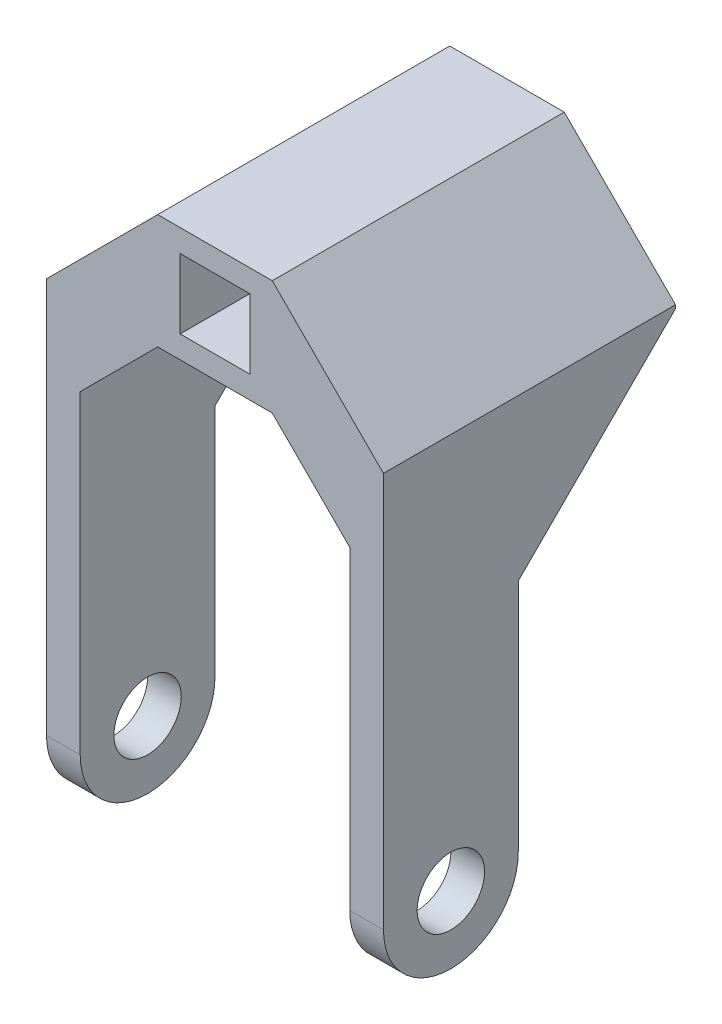
SolidWorks part; units mm, degrees
ref_plane "Front Plane" through (0, 0, 0) normal (0, 0, 1) x (1, 0, 0)
ref_plane "Top Plane" through (0, 0, 0) normal (0, 1, 0) x (1, 0, 0)
ref_plane "Right Plane" through (0, 0, 0) normal (1, 0, 0) x (0, 0, -1)
sketch "Sketch1" plane through (0, 0, 0) normal (0, 0, 1) x (1, 0, 0)
  line L1 (-50, 100) -> (50, 100) construction
  line L2 (-50, 100) -> (-50, -100) construction
  line L3 (-50, -100) -> (50, -100) construction
  line L4 (50, 100) -> (50, -100) construction
  line L5 (-50, 100) -> (50, -100)
  line L6 (-50, -100) -> (50, 100)
  point P0 (0, 0)
  dimension "D1" = 200
  dimension "D2" = 100
sketch "Sketch2" plane through (0, 0, 0) normal (0, 0, 1) x (1, 0, 0)
  line L0 (-25.5, 174.5) -> (25.5, 174.5)
  line L1 (-15.5, 215.5) -> (15.5, 215.5)
  line L2 (-15.5, 215.5) -> (-15.5, 184.5)
  line L3 (-15.5, 184.5) -> (15.5, 184.5)
  line L4 (15.5, 215.5) -> (15.5, 184.5)
  line L5 (-15.5, 215.5) -> (15.5, 184.5) construction
  line L6 (-15.5, 184.5) -> (15.5, 215.5) construction
  line L7 (25.5, 174.5) -> (60, 140)
  line L8 (60, 140) -> (60, -30)
  line L9 (60, -30) -> (75, -30)
  line L10 (75, -30) -> (75, 176)
  line L11 (75, 176) -> (25.5, 225.5)
  line L12 (25.5, 225.5) -> (-25.5, 225.5)
  line L13 (0, -110) -> (0, 110) construction
  line L14 (-60, -30) -> (-75, -30)
  line L15 (-60, 140) -> (-60, -30)
  line L16 (-75, -30) -> (-75, 176)
  line L17 (-25.5, 174.5) -> (-60, 140)
  line L18 (-75, 176) -> (-25.5, 225.5)
  point P0 (0, 200)
  point P10 (0, 0)
  point P15 (0, 0)
  point P23 (0, 174.5)
  point P24 (0, 225.5)
  dimension "D1" = 31
  dimension "D2" = 200
  dimension "D3" = 60
  dimension "D4" = 75
  dimension "D5" = 135
  dimension "D6" = 135
  dimension "D7" = 10
  dimension "D8" = 10
  dimension "D9" = 10
  dimension "D10" = 10
  dimension "D11" = 30
extrude "Boss-Extrude1" add sketch "Sketch2" along normal blind 30 and the other way blind 100
sketch "Sketch3" plane through (0, 0, 0) normal (1, 0, 0) x (0, 0, -1)
  line L0 (30, -30) -> (30, 104.5)
  line L1 (100, -30) -> (-30, -30) construction
  line L2 (30, 104.5) -> (100, 174.5)
  line L3 (100, 174.5) -> (100, -30)
  line L4 (100, -30) -> (100, 176) construction
  line L5 (100, -30) -> (30, -30)
  dimension "D1" = 30
  dimension "D2" = 45
extrude "Cut-Extrude1" cut sketch "Sketch3" against normal through all both and the other way through all
sketch "Sketch4" plane through (0, 0, 0) normal (1, 0, 0) x (0, 0, -1)
  circle A0 centre (0, 0) radius 15
  dimension "D1" = 30
extrude "Cut-Extrude2" cut sketch "Sketch4" against normal through all both and the other way through all
fillet "Fillet1" radius 30 4 edges at (67.5, -30, -30) (-67.5, -30, -30) (-67.5, -30, 30) (67.5, -30, 30)
